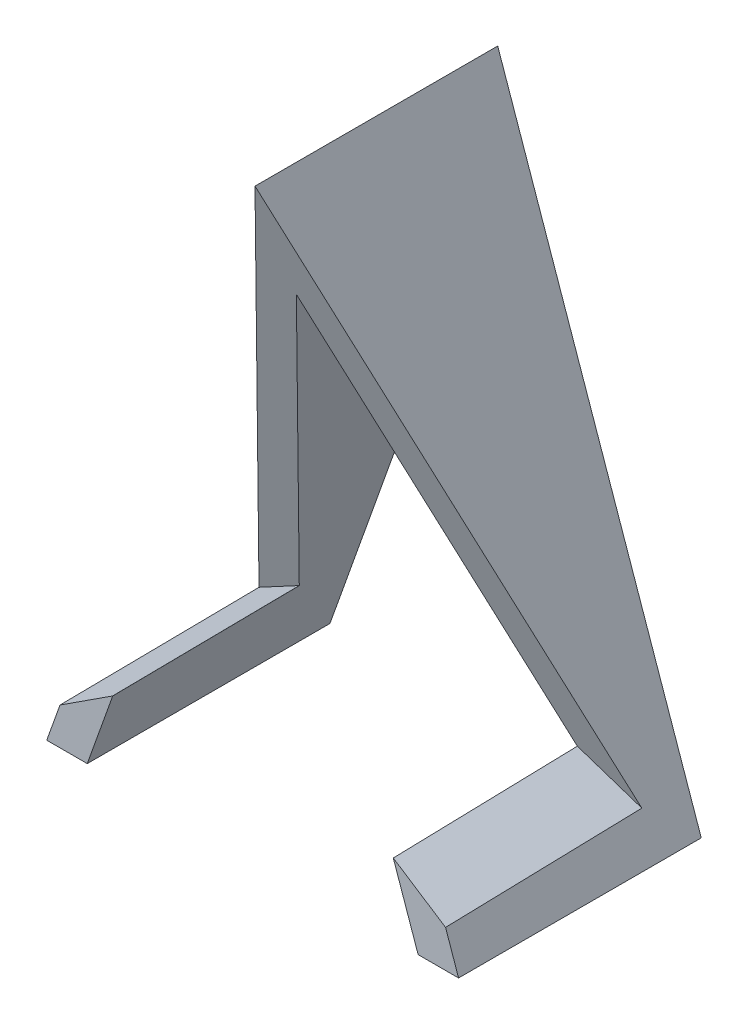
SolidWorks part; units mm, degrees
ref_plane "Plan de face" through (0, 0, 0) normal (0, 0, 1) x (1, 0, 0)
ref_plane "Plan de dessus" through (0, 0, 0) normal (0, 1, 0) x (1, 0, 0)
ref_plane "Plan de droite" through (0, 0, 0) normal (1, 0, 0) x (0, 0, -1)
sketch "Esquisse1" plane through (0, 0, 0) normal (0, 0, 1) x (1, 0, 0)
  line L0 (-20.6832, -25.5896) -> (0, 32.4104)
  line L1 (0, 32.4104) -> (20.2168, -25.5896)
  line L2 (20.2168, -25.5896) -> (25.2168, -25.5896)
  line L3 (25.2168, -25.5896) -> (0.0524, 46.6045)
  line L4 (0.0524, 46.6045) -> (-25.6925, -25.5896)
  line L5 (-25.6925, -25.5896) -> (-20.6832, -25.5896)
  point P2 (1.3079, 32.6011)
  point P7 (0.9659, 32.4104)
  dimension "D1" = 40.9
  dimension "D2" = 58
  dimension "D3" = 14.1941
  dimension "D4" = 5
  dimension "D5" = 5.0093
extrude "Boss.-Extru.1" add sketch "Esquisse1" along normal blind 30
sketch "Esquisse2" plane through (0, 0, 0) normal (1, 0, 0) x (0, 0, -1)
  line L0 (-30, 46.6045) -> (-7.0914, -16.3362)
  line L1 (-30, -25.5896) -> (-30, 46.6045) construction
  line L2 (-7.0914, -16.3362) -> (-30, -16.7772)
  line L3 (-30, -16.7772) -> (-30, 46.6045)
  line L4 (0, -25.5896) -> (0, 46.6045) construction
  point P7 (-6.3206, 0)
  point P8 (-30, 46.6045)
  dimension "D1" = 20
extrude "Enlèv. mat.-Extru.1" cut sketch "Esquisse2" against normal mid plane 80
chamfer "Chanfrein1" distance 5 angle 33 2 edges at (22.0683, -16.5567, 18.5457) (-22.4713, -16.5567, 18.5457) first distance on face at (19.5683, -16.5567, 18.5457) first distance on face at (-19.9666, -16.5567, 18.5457)
